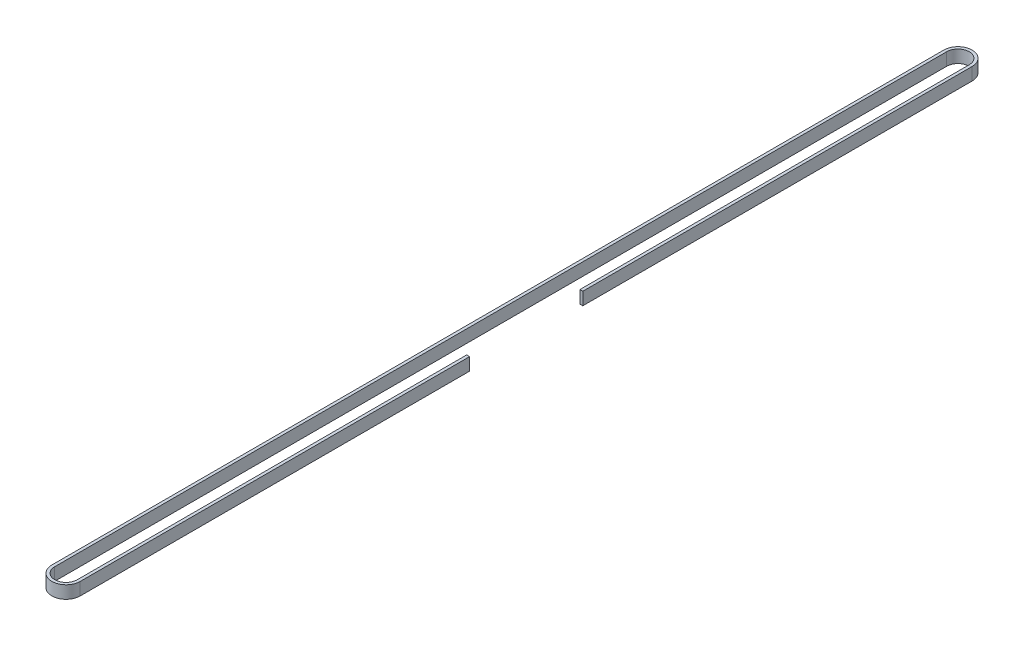
SolidWorks part; units mm, degrees
ref_plane "Front Plane" through (0, 0, 0) normal (0, 0, 1) x (1, 0, 0)
ref_plane "Top Plane" through (0, 0, 0) normal (0, 1, 0) x (1, 0, 0)
ref_plane "Right Plane" through (0, 0, 0) normal (1, 0, 0) x (0, 0, -1)
sketch "Sketch1" plane through (0, 0, 0) normal (0, 1, 0) x (1, 0, 0)
  line L0 (344.01, -294.7675) -> (344.01, 128.9825)
  line L1 (356.75, 128.9825) -> (356.75, -56.0175)
  line L2 (356.75, -294.7675) -> (356.75, -109.7675)
  arc A0 (356.75, -294.7675) -> (344.01, -294.7675) centre (350.38, -294.7675) cw
  arc A1 (356.75, 128.9825) -> (344.01, 128.9825) centre (350.38, 128.9825) ccw
  dimension "D1" = 6.37
  dimension "D2" = 423.75
  dimension "D3" = 185
extrude "Extrude-Thin1" add sketch "Sketch1" along normal blind 6 thin thin type two direction wall 0.376 second wall 1.004
